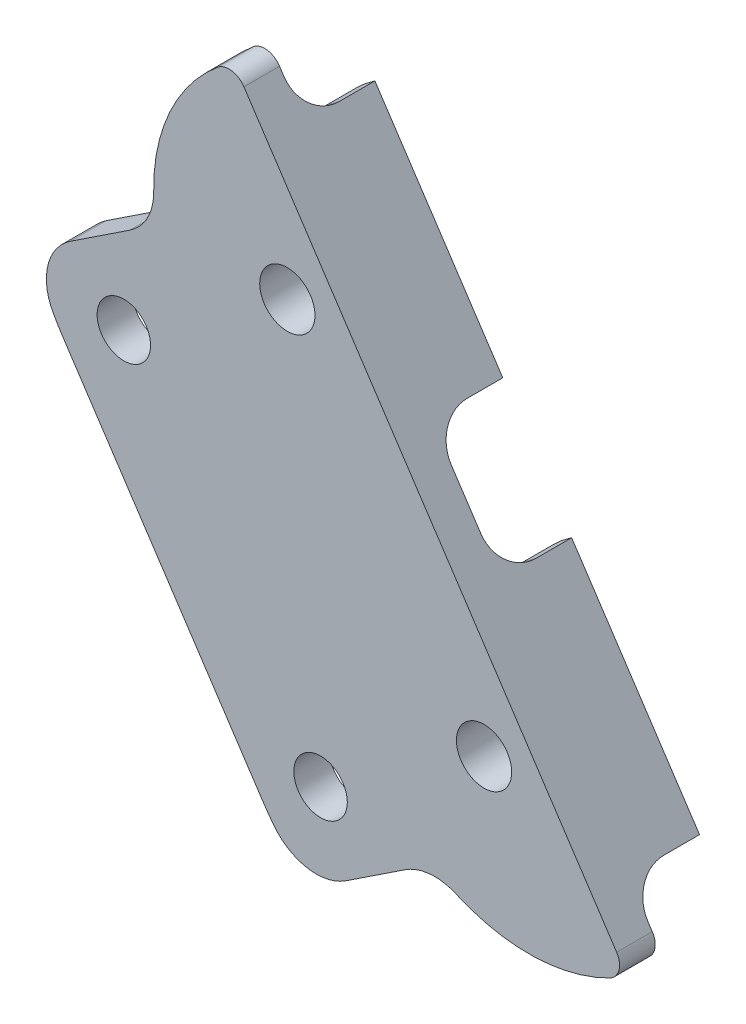
SolidWorks part; units mm, degrees
material "3003-H16"
ref_plane "前视基准面" through (0, 0, 0) normal (0, 0, 1) x (1, 0, 0)
ref_plane "上视基准面" through (0, 0, 0) normal (0, 1, 0) x (1, 0, 0)
ref_plane "右视基准面" through (0, 0, 0) normal (1, 0, 0) x (0, 0, -1)
other "Configuration Table"
sketch "草图2" plane through (0, 0, 0) normal (0, 0, 1) x (1, 0, 0)
  line L0 (14.565, -11.6696) -> (7.3898, -0.8291)
  line L1 (3.5263, 5.0081) -> (-3.6489, 15.8486)
  line L2 (-11.4038, 7.7177) -> (-14.736, 5.5122)
  line L3 (-15.0578, 0.5024) -> (-4.019, -16.1753)
  line L4 (0.7182, -17.8366) -> (4.0504, -15.6311)
  line L5 (15.9141, -13.7079) -> (15.1169, -12.5035)
  line L6 (6.8379, 0.0048) -> (4.0782, 4.1742)
  line L7 (-4.2009, 16.6825) -> (-4.998, 17.8869)
  line L8 (-4.2009, 16.6825) -> (-3.6489, 15.8486)
  line L9 (3.5263, 5.0081) -> (4.0782, 4.1742)
  line L10 (6.8379, 0.0048) -> (7.3898, -0.8291)
  line L11 (14.565, -11.6696) -> (15.1169, -12.5035)
  arc A0 (-11.4038, 7.7177) -> (-10.06, 10.2676) centre (-13.0597, 10.2194) ccw
  arc A1 (-14.736, 5.5122) -> (-15.6868, 1.5254) centre (-13.0802, 3.0106) ccw
  arc A2 (-15.6868, 1.5254) -> (-15.0578, 0.5024) centre (-0.0613, 10.4284) ccw
  arc A3 (-4.019, -16.1753) -> (-3.3232, -17.154) centre (10.9774, -6.2494) ccw
  arc A4 (-3.3232, -17.154) -> (0.7182, -17.8366) centre (-0.9376, -15.3349) ccw
  arc A5 (6.9226, -15.3904) -> (4.0504, -15.6311) centre (5.7062, -18.1327) ccw
  arc A6 (6.9226, -15.3904) -> (15.5361, -15.1498) centre (10.9774, -6.2494) ccw
  arc A7 (15.5361, -15.1498) -> (15.9141, -13.7079) centre (15.0802, -14.2598) ccw
  arc A10 (-4.998, 17.8869) -> (-6.4731, 18.1023) centre (-5.8319, 17.3349) ccw
  arc A11 (-6.4731, 18.1023) -> (-10.06, 10.2676) centre (-0.0613, 10.4284) ccw
  arc A12 (-1.2705, 9.628) -> (-3.8555, 7.917) centre (-2.563, 8.7725) ccw
  arc A13 (-3.8555, 7.917) -> (-1.2705, 9.628) centre (-2.563, 8.7725) ccw
  arc A14 (7.1832, -8.7607) -> (9.7683, -7.0497) centre (8.4757, -7.9052) ccw
  arc A15 (9.7683, -7.0497) -> (7.1832, -8.7607) centre (8.4757, -7.9052) ccw
  arc A16 (-1.9478, -14.8044) -> (0.5538, -13.1486) centre (-0.697, -13.9765) ccw
  arc A17 (0.5538, -13.1486) -> (-1.9478, -14.8044) centre (-0.697, -13.9765) ccw
  arc A18 (-10.4849, 3.5291) -> (-12.9866, 1.8733) centre (-11.7357, 2.7012) ccw
  arc A19 (-12.9866, 1.8733) -> (-10.4849, 3.5291) centre (-11.7357, 2.7012) ccw
extrude "凸台-拉伸1" add sketch "草图2" along normal blind 2
sketch "草图3" plane through (0, 0, 0) normal (0, 0, -1) x (-1, 0, 0)
  line L0 (3.6489, 15.8486) -> (-14.565, -11.6696)
  line L1 (-15.9141, -13.7079) -> (4.998, 17.8869) construction
  arc A0 (-3.5263, 5.0081) -> (3.6489, 15.8486) centre (0.0613, 10.4284) ccw
  arc A1 (-14.565, -11.6696) -> (-7.3898, -0.8291) centre (-10.9774, -6.2494) ccw
  circle A2 centre (2.563, 8.7725) radius 1.55
  circle A3 centre (-8.4757, -7.9052) radius 1.55
  line M2 (4.998, 17.8869) -> (-15.9141, -13.7079)
  circle M15 centre (2.563, 8.7725) radius 1.55
  circle M16 centre (-8.4757, -7.9052) radius 1.55
  dimension "D1" = 13
  dimension "D2" = 13
extrude "凸台-拉伸2" add sketch "草图3" along normal blind 4 contours A0 M2 M15 | A1 M2 M16 region at (-5.3514, 6.927, 0) region at (5.6874, -9.7508, 0)
fillet "圆角1" radius 2 2 edges at (5.5571, -9.837, 0) (-5.4816, 6.8408, 0)
